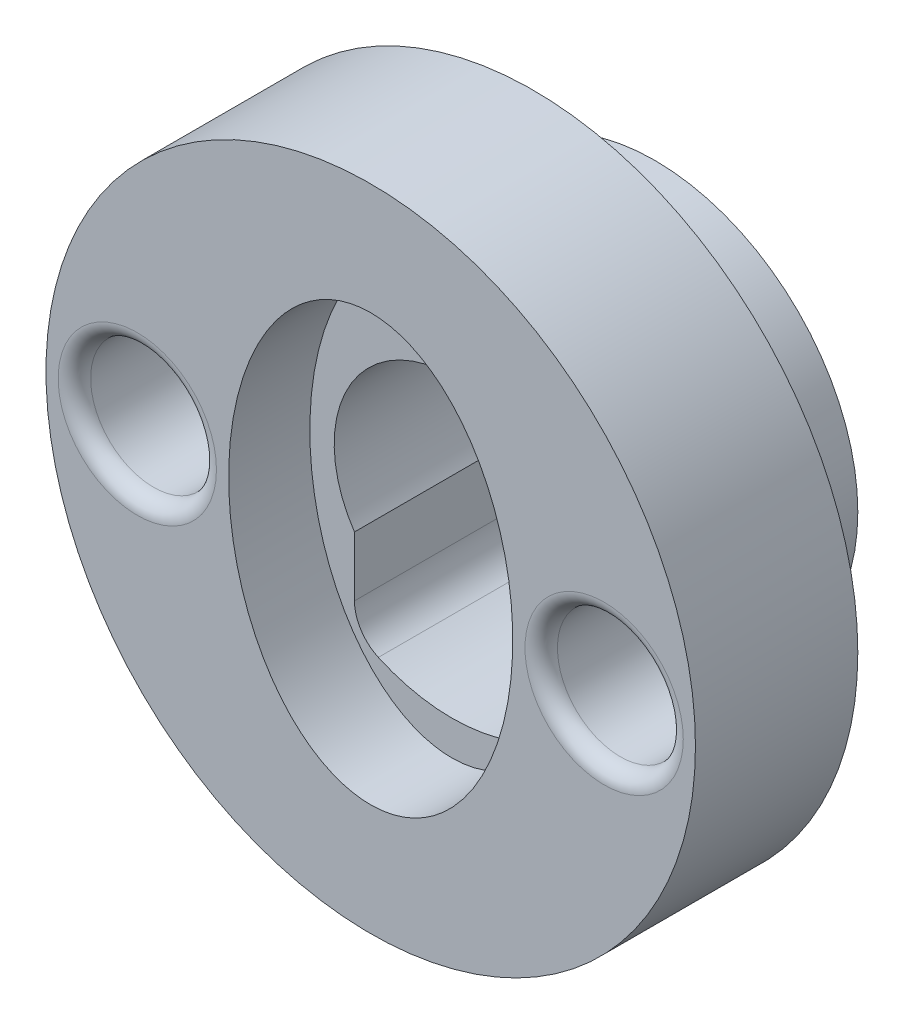
SolidWorks part; units mm, degrees
ref_plane "Front Plane" through (0, 0, 0) normal (0, 0, 1) x (1, 0, 0)
ref_plane "Top Plane" through (0, 0, 0) normal (0, 1, 0) x (1, 0, 0)
ref_plane "Right Plane" through (0, 0, 0) normal (1, 0, 0) x (0, 0, -1)
sketch "Sketch1" plane through (0, 0, 0) normal (0, 0, 1) x (1, 0, 0)
  circle A0 centre (0, 0) radius 1
  circle A1 centre (0, 0) radius 5
  dimension "D1" = 2
  dimension "D2" = 10
extrude "Boss-Extrude1" add sketch "Sketch1" along normal blind 3
sketch "Sketch2" plane through (0, 0, 3) normal (0, 0, 1) x (1, 0, 0)
  circle A0 centre (0, 0) radius 8
  dimension "D1" = 16
extrude "Boss-Extrude2" add sketch "Sketch2" along normal blind 4
sketch "Sketch4" plane through (0, 0, 3) normal (0, 0, -1) x (-1, 0, 0)
  circle A1 centre (0, 0) radius 1
  circle A2 centre (0, 0) radius 1
  dimension "D1" = 0
extrude "Cut-Extrude2" cut sketch "Sketch4" against normal blind 8
sketch "Sketch3" plane through (0, 0, 7) normal (0, 0, 1) x (1, 0, 0)
  line L0 (0, -5.25) -> (0, 5.25) construction
  ellipse E0 centre (0, 0) end of major axis (0, -5.25) minor radius 3.5
  dimension "D1" = 10.5
  dimension "D2" = 7
extrude "Cut-Extrude1" cut sketch "Sketch3" against normal blind 2
sketch "Sketch7" plane through (0, 0, 0) normal (0, 0, -1) x (-1, 0, 0)
  circle A0 centre (0, 0) radius 5 construction
  arc A1 (1.7219, 1.6718) -> (1.6537, 1.7393) centre (0, 0) ccw
  circle A2 centre (0, 0) radius 5
  arc A3 (1.2066, 0.8894) -> (1.7219, 1.6718) centre (0.9227, 1.6373) ccw
  arc A4 (1.8193, 1.7146) -> (1.6955, 1.8372) centre (0, 0) ccw
  arc A5 (1.6537, 1.7393) -> (0.8767, 1.2159) centre (1.6276, 0.9398) ccw
  arc A6 (1.6955, 1.8372) -> (0.834, 1.3643) centre (1.6276, 0.9398) ccw
  arc A7 (0.8767, 1.2159) -> (0.4534, 1.4288) centre (0, 0) ccw
  arc A8 (0.834, 1.3643) -> (0.598, 1.483) centre (0, 0) ccw
  arc A9 (0.4534, 1.4288) -> (0.4104, 2.3647) centre (-0.2159, 1.8669) ccw
  arc A10 (0.598, 1.483) -> (0.464, 2.4566) centre (-0.2159, 1.8669) ccw
  arc A11 (0.4104, 2.3647) -> (0.3155, 2.3792) centre (0, 0) ccw
  arc A12 (0.464, 2.4566) -> (0.2918, 2.4829) centre (0, 0) ccw
  arc A13 (0.3155, 2.3792) -> (-0.0054, 1.499) centre (0.7644, 1.7169) ccw
  arc A14 (0.2918, 2.4829) -> (-0.1272, 1.5939) centre (0.7644, 1.7169) ccw
  arc A15 (-0.0054, 1.499) -> (-0.473, 1.4224) centre (0, 0) ccw
  arc A16 (-0.1272, 1.5939) -> (-0.3878, 1.5513) centre (0, 0) ccw
  arc A17 (-0.473, 1.4224) -> (-1.0579, 2.1543) centre (-1.2721, 1.3835) ccw
  arc A18 (-0.3878, 1.5513) -> (-1.0685, 2.2601) centre (-1.2721, 1.3835) ccw
  arc A19 (-1.0579, 2.1543) -> (-1.1432, 2.1103) centre (0, 0) ccw
  arc A20 (-1.0685, 2.2601) -> (-1.2233, 2.1802) centre (0, 0) ccw
  arc A21 (-1.1432, 2.1103) -> (-0.8854, 1.2095) centre (-0.3908, 1.8383) ccw
  arc A22 (-1.2233, 2.1802) -> (-1.0398, 1.2148) centre (-0.3908, 1.8383) ccw
  arc A23 (-0.8854, 1.2095) -> (-1.2187, 0.8727) centre (0, 0) ccw
  arc A24 (-1.0398, 1.2148) -> (-1.2256, 1.027) centre (0, 0) ccw
  arc A25 (-1.2187, 0.8727) -> (-2.1221, 1.121) centre (-1.8423, 0.3715) ccw
  arc A26 (-1.2256, 1.027) -> (-2.1929, 1.2004) centre (-1.8423, 0.3715) ccw
  arc A27 (-2.1221, 1.121) -> (-2.1652, 1.0353) centre (0, 0) ccw
  arc A28 (-2.1929, 1.2004) -> (-2.2712, 1.0448) centre (0, 0) ccw
  arc A29 (-2.1652, 1.0353) -> (-1.4273, 0.4581) centre (-1.3967, 1.2575) ccw
  arc A30 (-2.2712, 1.0448) -> (-1.5552, 0.3716) centre (-1.3967, 1.2575) ccw
  arc A31 (-1.4273, 0.4581) -> (-1.499, -0.0103) centre (0, 0) ccw
  arc A32 (-1.5552, 0.3716) -> (-1.5952, 0.1105) centre (0, 0) ccw
  arc A33 (-1.499, -0.0103) -> (-2.3757, -0.3404) centre (-1.7088, -0.7823) ccw
  arc A34 (-1.5952, 0.1105) -> (-2.4797, -0.3178) centre (-1.7088, -0.7823) ccw
  arc A35 (-2.3757, -0.3404) -> (-2.3602, -0.4351) centre (0, 0) ccw
  arc A36 (-2.4797, -0.3178) -> (-2.4516, -0.4897) centre (0, 0) ccw
  arc A37 (-2.3602, -0.4351) -> (-1.424, -0.4683) centre (-1.8691, 0.1964) ccw
  arc A38 (-2.4516, -0.4897) -> (-1.4766, -0.6135) centre (-1.8691, 0.1964) ccw
  arc A39 (-1.424, -0.4683) -> (-1.2066, -0.8894) centre (0, 0) ccw
  arc A40 (-1.4766, -0.6135) -> (-1.3555, -0.8482) centre (0, 0) ccw
  arc A41 (-1.2066, -0.8894) -> (-1.7219, -1.6718) centre (-0.9227, -1.6373) ccw
  arc A42 (-1.3555, -0.8482) -> (-1.8193, -1.7146) centre (-0.9227, -1.6373) ccw
  arc A43 (-1.7219, -1.6718) -> (-1.6537, -1.7393) centre (0, 0) ccw
  arc A44 (-1.8193, -1.7146) -> (-1.6955, -1.8372) centre (0, 0) ccw
  arc A45 (-1.6537, -1.7393) -> (-0.8767, -1.2159) centre (-1.6276, -0.9398) ccw
  arc A46 (-1.6955, -1.8372) -> (-0.834, -1.3643) centre (-1.6276, -0.9398) ccw
  arc A47 (-0.8767, -1.2159) -> (-0.4534, -1.4288) centre (0, 0) ccw
  arc A48 (-0.834, -1.3643) -> (-0.598, -1.483) centre (0, 0) ccw
  arc A49 (-0.4534, -1.4288) -> (-0.4104, -2.3647) centre (0.2159, -1.8669) ccw
  arc A50 (-0.598, -1.483) -> (-0.464, -2.4566) centre (0.2159, -1.8669) ccw
  arc A51 (-0.4104, -2.3647) -> (-0.3155, -2.3792) centre (0, 0) ccw
  arc A52 (-0.464, -2.4566) -> (-0.2918, -2.4829) centre (0, 0) ccw
  arc A53 (-0.3155, -2.3792) -> (0.0054, -1.499) centre (-0.7644, -1.7169) ccw
  arc A54 (-0.2918, -2.4829) -> (0.1272, -1.5939) centre (-0.7644, -1.7169) ccw
  arc A55 (0.0054, -1.499) -> (0.473, -1.4224) centre (0, 0) ccw
  arc A56 (0.1272, -1.5939) -> (0.3878, -1.5513) centre (0, 0) ccw
  arc A57 (0.473, -1.4224) -> (1.0579, -2.1543) centre (1.2721, -1.3835) ccw
  arc A58 (0.3878, -1.5513) -> (1.0685, -2.2601) centre (1.2721, -1.3835) ccw
  arc A59 (1.0579, -2.1543) -> (1.1432, -2.1103) centre (0, 0) ccw
  arc A60 (1.0685, -2.2601) -> (1.2233, -2.1802) centre (0, 0) ccw
  arc A61 (1.1432, -2.1103) -> (0.8854, -1.2095) centre (0.3908, -1.8383) ccw
  arc A62 (1.2233, -2.1802) -> (1.0398, -1.2148) centre (0.3908, -1.8383) ccw
  arc A63 (0.8854, -1.2095) -> (1.2187, -0.8727) centre (0, 0) ccw
  arc A64 (1.0398, -1.2148) -> (1.2256, -1.027) centre (0, 0) ccw
  arc A65 (1.2187, -0.8727) -> (2.1221, -1.121) centre (1.8423, -0.3715) ccw
  arc A66 (1.2256, -1.027) -> (2.1929, -1.2004) centre (1.8423, -0.3715) ccw
  arc A67 (2.1221, -1.121) -> (2.1652, -1.0353) centre (0, 0) ccw
  arc A68 (2.1929, -1.2004) -> (2.2712, -1.0448) centre (0, 0) ccw
  arc A69 (2.1652, -1.0353) -> (1.4273, -0.4581) centre (1.3967, -1.2575) ccw
  arc A70 (2.2712, -1.0448) -> (1.5552, -0.3716) centre (1.3967, -1.2575) ccw
  arc A71 (1.4273, -0.4581) -> (1.499, 0.0103) centre (0, 0) ccw
  arc A72 (1.5552, -0.3716) -> (1.5952, -0.1105) centre (0, 0) ccw
  arc A73 (1.499, 0.0103) -> (2.3757, 0.3404) centre (1.7088, 0.7823) ccw
  arc A74 (1.5952, -0.1105) -> (2.4797, 0.3178) centre (1.7088, 0.7823) ccw
  arc A75 (2.3757, 0.3404) -> (2.3602, 0.4351) centre (0, 0) ccw
  arc A76 (2.4797, 0.3178) -> (2.4516, 0.4897) centre (0, 0) ccw
  arc A77 (2.3602, 0.4351) -> (1.424, 0.4683) centre (1.8691, -0.1964) ccw
  arc A78 (2.4516, 0.4897) -> (1.4766, 0.6135) centre (1.8691, -0.1964) ccw
  arc A79 (1.424, 0.4683) -> (1.2066, 0.8894) centre (0, 0) ccw
  arc A80 (1.4766, 0.6135) -> (1.3555, 0.8482) centre (0, 0) ccw
  arc A82 (1.3555, 0.8482) -> (1.8193, 1.7146) centre (0.9227, 1.6373) ccw
  point P81 (0, 0)
  point P84 (0, 0)
  circle M87 centre (0, 0) radius 1
  dimension "D1" = 0.1
extrude "Cut-Extrude3" [suppressed] cut sketch "Sketch7" against normal up to surface (6 mm away) contours A77 A79 A3 A1 A5 A7 A9 A11 A13 A15 A17 A19 A21 A23 A25 A27 A29 A31 A33 A35 A37 A39 A41 A43 A45 A47 A49 A51 A53 A55 A57 A59 A61 A63 A65 A67 A69 A71 A73 A75 M87 | A80 A82 A4 A6 A8 A10 A12 A14 A16 A18 A20 A22 A24 A26 A28 A30 A32 A34 A36 A38 A40 A42 A44 A46 A48 A50 A52 A54 A56 A58 A60 A62 A64 A66 A68 A70 A72 A74 A76 A78 A79 A77 A75 A73 A71 A69 A67 A65 A63 A61
sketch "Sketch10" plane through (0, 0, 0) normal (0, 0, -1) x (-1, 0, 0)
  line L7 (2.25, 4.25) -> (-2.25, 4.25)
  line L8 (2.25, 4.25) -> (2.25, -4.25)
  line L9 (2.25, -4.25) -> (-2.25, -4.25)
  line L10 (-2.25, 4.25) -> (-2.25, -4.25)
  line L11 (2.25, 4.25) -> (-2.25, -4.25) construction
  line L12 (2.25, -4.25) -> (-2.25, 4.25) construction
  circle A1 centre (0, 0) radius 4.25
  circle A3 centre (0, 0) radius 2.75
  dimension "D2" = 5.5
  dimension "D1" = 8.5
  dimension "D3" = 4.5
extrude "Cut-Extrude5" cut sketch "Sketch10" against normal up to surface (7 mm away) contours A3 L10 A1 L8 | A3 region at (0, -3.1989, 0) up to face at (0, -5.25, 7)
sketch "Sketch9" plane through (0, 0, 7) normal (0, 0, 1) x (1, 0, 0)
  line L0 (5.75, 0) -> (-5.75, 0) construction
  circle A0 centre (5.75, 0) radius 1.55
  circle A1 centre (-5.75, 0) radius 1.55
  circle A2 centre (0, 0) radius 8 construction
  circle A3 centre (0, 0) radius 8
  dimension "D1" = 3.1
  dimension "D2" = 3.1
  dimension "D3" = 5.75
  dimension "D4" = 5.75
extrude "Cut-Extrude4" cut sketch "Sketch9" against normal blind 3.5 contours A1 | A0 region at (5.75, 0, 7) region at (-5.75, 0, 7)
sketch "Sketch11" plane through (0, 0, 0) normal (1, 0, 0) x (0, 0, -1)
  line L0 (-3, -8) -> (-7, -8)
  line L1 (-7, 8) -> (-3, 8)
  line L2 (-7, 8) -> (-3, 8)
  line L3 (-3, -8) -> (-7, -8)
  line L4 (-3, -8) -> (-3, 8) construction
  line L5 (-3, -8) -> (-3, 8)
  line L6 (-7, 8) -> (-7, -8) construction
  line L7 (-7, 8) -> (-7, -8)
  line L8 (0, 5) -> (-3, 5) construction
  line L9 (0, 5) -> (-3, 5)
  line L10 (-3, -5) -> (0, -5) construction
  line L11 (-3, -5) -> (0, -5)
  circle A0 centre (-5, 5.5) radius 0.5
  circle A1 centre (-5, -5.5) radius 0.5
  dimension "D1" = 2.5
  dimension "D5" = 1
  dimension "D6" = 1
  dimension "D2" = 2
  dimension "D3" = 2
  dimension "D4" = 2.5
extrude "Cut-Extrude6" [suppressed] cut sketch "Sketch11" against normal blind 10 and the other way blind 10 contours A0 | A1
ref_plane "Plane1" [suppressed] through (3, 0, 0) normal (1, 0, 0) x (0, 0, -1)
sketch "Sketch12" [suppressed] plane through (3, 0, 0) normal (1, 0, 0) x (0, 0, -1)
  circle A0 centre (-5, -5.5) radius 0.5
  circle A2 centre (-5, -5.5) radius 0.5
  circle A4 centre (-5, 5.5) radius 1.1
  circle A6 centre (-5, -5.5) radius 1.1
  circle A7 centre (-5, 5.5) radius 0.5
  circle A8 centre (-5, 5.5) radius 0.5
extrude "Cut-Extrude7" [suppressed] cut sketch "Sketch12" along normal blind 10
ref_plane "Plane2" [suppressed] through (-2, 0, 0) normal (1, 0, 0) x (0, 0, -1)
sketch "Sketch13" [suppressed] plane through (-2, 0, 0) normal (1, 0, 0) x (0, 0, -1)
  line L1 (-6.625, 3.8735) -> (-3.375, 3.8735) construction
  line L2 (-6.625, 3.8735) -> (-6.625, 7.1265) construction
  line L3 (-6.625, 7.1265) -> (-3.375, 7.1265) construction
  line L4 (-3.375, 3.8735) -> (-3.375, 7.1265) construction
  line L5 (-6.625, 3.8735) -> (-3.375, 7.1265) construction
  line L6 (-6.625, 7.1265) -> (-3.375, 3.8735) construction
  line L13 (-3.375, -7.125) -> (-6.625, -7.125) construction
  line L14 (-3.375, -7.125) -> (-3.375, -3.875) construction
  line L15 (-3.375, -3.875) -> (-6.625, -3.875) construction
  line L16 (-6.625, -7.125) -> (-6.625, -3.875) construction
  line L17 (-3.375, -7.125) -> (-6.625, -3.875) construction
  line L18 (-3.375, -3.875) -> (-6.625, -7.125) construction
  line L19 (-4.0618, -7.125) -> (-3.1236, -5.5)
  line L20 (-3.1236, -5.5) -> (-4.0618, -3.875)
  line L21 (-4.0618, -3.875) -> (-5.9382, -3.875)
  line L22 (-5.9382, -3.875) -> (-6.8764, -5.5)
  line L23 (-6.8764, -5.5) -> (-5.9382, -7.125)
  line L24 (-5.9382, -7.125) -> (-4.0618, -7.125)
  line L25 (-4.0609, 7.1265) -> (-5.9391, 7.1265)
  line L26 (-5.9391, 7.1265) -> (-6.8781, 5.5)
  line L27 (-6.8781, 5.5) -> (-5.9391, 3.8735)
  line L28 (-5.9391, 3.8735) -> (-4.0609, 3.8735)
  line L29 (-4.0609, 3.8735) -> (-3.1219, 5.5)
  line L30 (-3.1219, 5.5) -> (-4.0609, 7.1265)
  circle A0 centre (-5, 5.5) radius 0.5
  circle A1 centre (-5, 5.5) radius 0.5
  circle A2 centre (-5, -5.5) radius 0.5
  circle A3 centre (-5, -5.5) radius 0.5 construction
  circle A4 centre (-5, 5.5) radius 1.6265 construction
  circle A5 centre (-5, -5.5) radius 1.625 construction
  dimension "D1" = 3.25
  dimension "D2" = 3.253
  dimension "D3" = 3.25
  dimension "D4" = 3.25
extrude "Cut-Extrude8" [suppressed] cut sketch "Sketch13" against normal blind 10
fillet "Fillet2" [suppressed] radius 0.1
split "Split1" [suppressed] bodies to split 112
sketch "Sketch14" plane through (0, 0, 5) normal (0, 0, 1) x (1, 0, 0)
  line L0 (2.25, -3.6056) -> (2.25, -1.5811) construction
  line L1 (-2.25, -3.6056) -> (-2.25, -1.5811) construction
  line L2 (2.25, -3.6056) -> (2.25, -1.5811)
  line L3 (-2.25, -3.6056) -> (-2.25, -1.5811)
  line L4 (-2.4, -3.6878) -> (-2.4, -1.6279)
  line L5 (2.4, -3.6878) -> (2.4, -1.6279)
  arc A0 (2.25, -1.5811) -> (-2.25, -1.5811) centre (0, 0) ccw construction
  arc A1 (-2.25, -3.6056) -> (2.25, -3.6056) centre (0, 0) ccw construction
  arc A2 (2.25, -1.5811) -> (-2.25, -1.5811) centre (0, 0) ccw
  arc A3 (-2.25, -3.6056) -> (2.25, -3.6056) centre (0, 0) ccw
  arc A4 (2.4, -1.6279) -> (-2.4, -1.6279) centre (0, 0) ccw
  arc A5 (-2.4, -3.6878) -> (2.4, -3.6878) centre (0, 0) ccw
  dimension "D1" = 0.15
extrude "Cut-Extrude9" cut sketch "Sketch14" against normal blind 10
fillet "Fillet3" radius 1 2 edges at (-2.4, -3.6878, 2.5) (2.4, -3.6878, 2.5)
fillet "Fillet1" radius 0.4 2 edges at (-4.2, 0, 7) (7.3, 0, 7)
